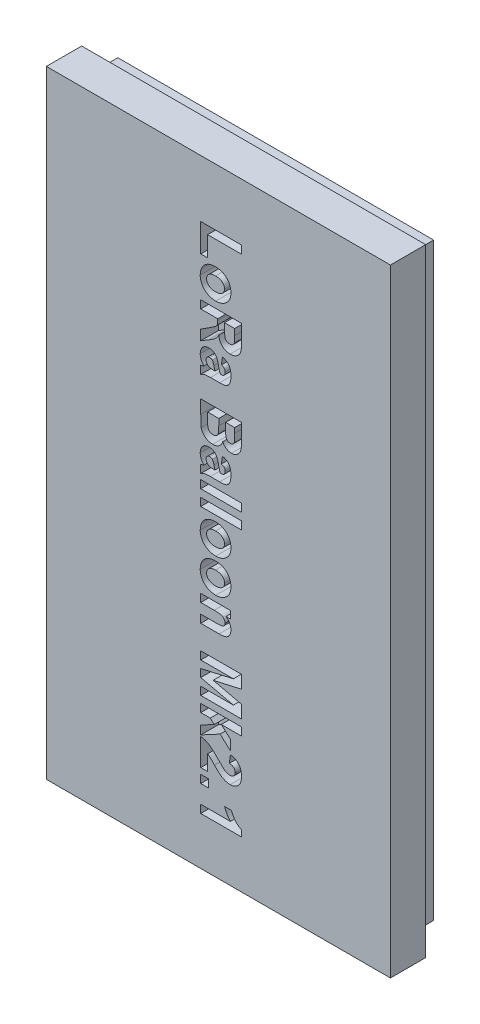
SolidWorks part; units mm, degrees
ref_plane "Front Plane" through (0, 0, 0) normal (0, 0, 1) x (1, 0, 0)
ref_plane "Top Plane" through (0, 0, 0) normal (0, 1, 0) x (1, 0, 0)
ref_plane "Right Plane" through (0, 0, 0) normal (1, 0, 0) x (0, 0, -1)
sketch "Sketch1" plane through (0, 0, 0) normal (0, 0, 1) x (1, 0, 0)
  line L1 (0, 0) -> (39, 0)
  line L2 (0, 0) -> (0, 70)
  line L3 (0, 70) -> (39, 70)
  line L4 (39, 0) -> (39, 70)
  dimension "D1" = 70
  dimension "D2" = 39
extrude "Boss-Extrude1" add sketch "Sketch1" along normal blind 4
sketch "Sketch2" plane through (0, 0, 0) normal (0, 0, -1) x (-1, 0, 0)
  line L0 (-39, 0) -> (-39, 70) construction
  line L1 (-37.4, 68.4) -> (-35.6, 68.4)
  line L2 (-37.4, 68.4) -> (-37.4, 1.6)
  line L3 (-37.4, 1.6) -> (-35.6, 1.6)
  line L4 (-35.6, 68.4) -> (-35.6, 1.6)
  line L5 (0, 0) -> (-39, 0) construction
  line L6 (0, 70) -> (0, 0) construction
  line L7 (-35.6, 1.6) -> (-1.6, 1.6)
  line L8 (-35.6, 1.6) -> (-35.6, 3.4)
  line L9 (-35.6, 3.4) -> (-1.6, 3.4)
  line L10 (-1.6, 1.6) -> (-1.6, 3.4)
  line L12 (-39, 70) -> (0, 70) construction
  line L13 (-39, 35) -> (0, 35) construction
  line L14 (-19.5, 70) -> (-19.5, 0) construction
  line L15 (-35.6, 66.6) -> (-1.6, 66.6)
  line L16 (-1.6, 68.4) -> (-1.6, 66.6)
  line L17 (-35.6, 68.4) -> (-1.6, 68.4)
  line L18 (-35.6, 68.4) -> (-35.6, 66.6)
  line L19 (-1.6, 1.6) -> (-3.4, 1.6)
  line L20 (-3.4, 68.4) -> (-3.4, 1.6)
  line L21 (-1.6, 68.4) -> (-3.4, 68.4)
  line L22 (-1.6, 68.4) -> (-1.6, 1.6)
  dimension "D1" = 1.6
  dimension "D2" = 1.8
  dimension "D3" = 1.6
  dimension "D4" = 1.8
extrude "Boss-Extrude2" add sketch "Sketch2" along normal blind 2.5 contours L4 L1 L2 L3 | L22 L15 L20 L9 | L20 L9 L4 L7 | L9 L20 L7 L10 | L17 L20 L15 L16 | L20 L17 L4 L15 region at (36.5, 35, 0) region at (19.5, 67.5, 0) region at (2.5, 67.5, 0) region at (19.5, 2.5, 0) region at (2.5, 35, 0) region at (2.5, 2.5, 0)
sketch "Sketch3" plane through (0, 0, 4) normal (0, 0, 1) x (1, 0, 0)
  line L0 (17.5, 0) -> (17.5, 64) construction
  line L4 (0, 0) -> (39, 0) construction
  line L6 (0, 70) -> (0, 0) construction
  text T0 "<b>LoRa Balloon Mk2.1</b>" font "Arial Narrow" height in points 18
  dimension "D1" = 17.5
  dimension "D2" = 64
extrude "Cut-Extrude1" cut sketch "Sketch3" against normal blind 2
